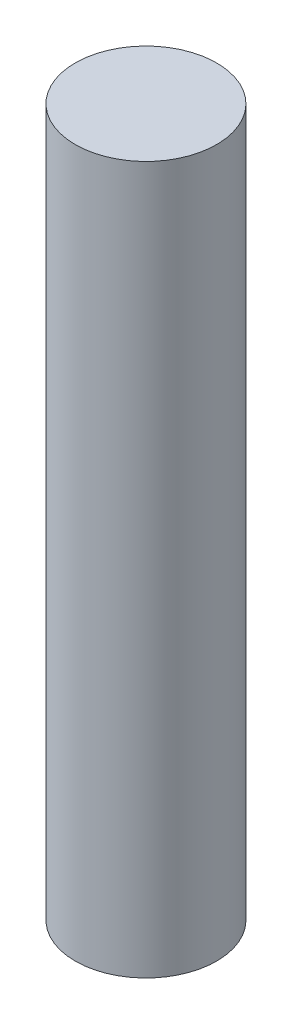
SolidWorks part; units mm, degrees
ref_plane "前视基准面" through (0, 0, 0) normal (0, 0, 1) x (1, 0, 0)
ref_plane "上视基准面" through (0, 0, 0) normal (0, 1, 0) x (1, 0, 0)
ref_plane "右视基准面" through (0, 0, 0) normal (1, 0, 0) x (0, 0, -1)
other "Configuration Table"
sketch "草图1" plane through (0, 0, 0) normal (0, 1, 0) x (1, 0, 0)
  circle A0 centre (0, 0) radius 150
  dimension "D1" = 300
extrude "凸台-拉伸1" add sketch "草图1" along normal blind 1500
ref_axis "基准轴1" through (0, 1500, 0) along (0, -1, 0)
